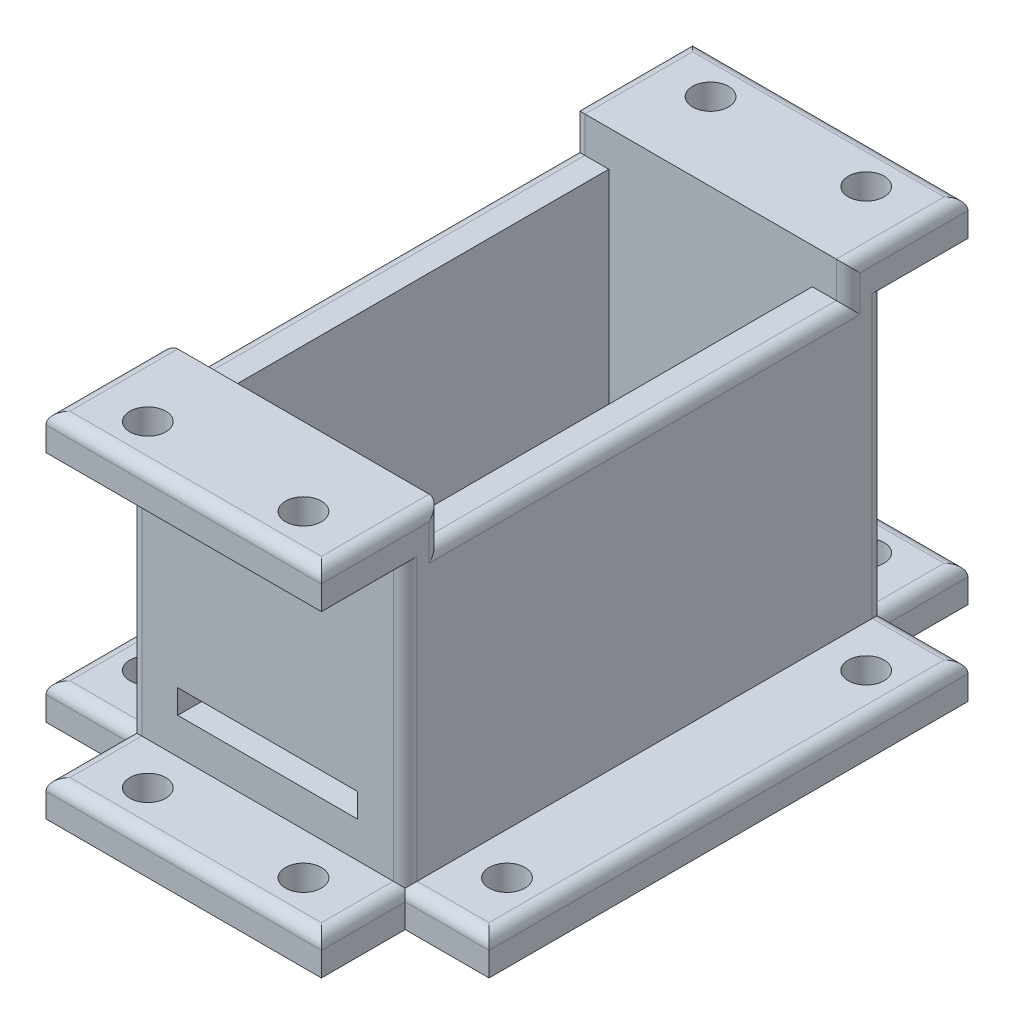
SolidWorks part; units mm, degrees
ref_plane "Alzado" through (0, 0, 0) normal (0, 0, 1) x (1, 0, 0)
ref_plane "Planta" through (0, 0, 0) normal (0, 1, 0) x (1, 0, 0)
ref_plane "Vista lateral" through (0, 0, 0) normal (1, 0, 0) x (0, 0, -1)
sketch "Croquis2" plane through (0, 0, 0) normal (0, 1, 0) x (1, 0, 0)
  line L1 (0, 0) -> (-23, 0)
  line L2 (0, 0) -> (0, 40)
  line L3 (0, 40) -> (-23, 40)
  line L4 (-23, 0) -> (-23, 40)
  dimension "D1" = 40
  dimension "D2" = 23
extrude "Saliente-Extruir1" add sketch "Croquis2" along normal blind 23.5
sketch "Croquis3" plane through (0, 23.5, 0) normal (0, 1, 0) x (1, 0, 0)
  line L0 (0, 40) -> (-23, 40) construction
  line L1 (-20, 37) -> (-3, 37)
  line L2 (-20, 37) -> (-20, 3)
  line L3 (-20, 3) -> (-3, 3)
  line L4 (-3, 37) -> (-3, 3)
  line L5 (-23, 40) -> (-23, 0) construction
  line L6 (-23, 0) -> (0, 0) construction
  line L7 (0, 0) -> (0, 40) construction
  dimension "D1" = 3
  dimension "D2" = 3
  dimension "D3" = 3
  dimension "D4" = 3
extrude "Cortar-Extruir1" cut sketch "Croquis3" against normal blind 13.5
sketch "Croquis4" plane through (0, 0, 0) normal (0, -1, 0) x (1, 0, 0)
  line L1 (0, -40) -> (-23, -40) construction
  line L2 (-17, -40) -> (-30, -40)
  line L3 (-17, -40) -> (-17, 0)
  line L4 (-17, 0) -> (-30, 0)
  line L5 (-30, -40) -> (-30, 0)
  line L6 (-23, -40) -> (-23, 0) construction
  line L7 (-23, -40) -> (-23, 0) construction
  line L8 (-23, -6) -> (0, -6)
  line L9 (-23, -6) -> (-23, 7)
  line L10 (-23, 7) -> (0, 7)
  line L11 (0, -6) -> (0, 7)
  line L12 (-23, 0) -> (0, 0) construction
  line L13 (0, 0) -> (0, -40) construction
  line L14 (-6, -40) -> (7, -40)
  line L15 (-6, -40) -> (-6, 0)
  line L16 (-6, 0) -> (7, 0)
  line L17 (7, -40) -> (7, 0)
  line L19 (-23, -34) -> (0, -34)
  line L20 (-23, -34) -> (-23, -47)
  line L21 (-23, -47) -> (0, -47)
  line L22 (0, -34) -> (0, -47)
  point P7 (-23, -20)
  line M13 (0, -40) -> (0, 0)
  line M14 (0, 0) -> (-23, 0)
  line M15 (-23, 0) -> (-23, -40)
  line M16 (-23, -40) -> (0, -40)
  dimension "D1" = 7
  dimension "D2" = 7
  dimension "D3" = 7
  dimension "D4" = 7
  dimension "D5" = 13
  dimension "D6" = 23
  dimension "D7" = 40
  dimension "D8" = 40
  dimension "D9" = 23
  dimension "D10" = 13
  dimension "D11" = 13
  dimension "D12" = 13
extrude "Saliente-Extruir6" add sketch "Croquis4" along normal blind 3 contours L19 L3 L8 M15 | L8 L3 M15 M14 | L5 L2 L4 M15 | L11 L10 L9 M14 | L19 L3 M15 M16 | L19 L3 L15 M16 | L19 L15 M16 M13 | L15 L19 L8 M13 | L15 L8 M13 M14 | L8 L15 L3 M14 | L14 L17 L16 M13
sketch "Croquis6" plane through (0, 0, 0) normal (0, 1, 0) x (1, 0, 0)
  line L0 (-30, 40) -> (-30, 0) construction
  line L1 (-30, 40) -> (-23, 40) construction
  line L2 (-23, 0) -> (-30, 0) construction
  line L3 (-23, 40) -> (-23, 47) construction
  line L4 (0, 40) -> (0, 47) construction
  line L5 (-23, 47) -> (0, 47) construction
  line L6 (-30, 20) -> (15.9373, 20) construction
  line L7 (-11.5, 47) -> (-11.5, -15.5258) construction
  circle A0 centre (-26.5, 5) radius 1.5
  circle A1 centre (-26.5, 35) radius 1.5
  circle A2 centre (-18, 43.5) radius 1.5
  circle A3 centre (-5, 43.5) radius 1.5
  circle A4 centre (3.5, 5) radius 1.5
  circle A5 centre (3.5, 35) radius 1.5
  circle A6 centre (-5, -3.5) radius 1.5
  circle A7 centre (-18, -3.5) radius 1.5
  dimension "D1" = 3
  dimension "D2" = 3
  dimension "D3" = 3.5
  dimension "D5" = 5
  dimension "D6" = 3.5
  dimension "D7" = 3
  dimension "D8" = 3
  dimension "D9" = 5
  dimension "D10" = 5
  dimension "D11" = 3.5
  dimension "D12" = 3.5
  dimension "D4" = 5
extrude "Cortar-Extruir2" cut sketch "Croquis6" against normal through all
sketch "Croquis7" plane through (0, 23.5, 0) normal (0, 1, 0) x (1, 0, 0)
  line L1 (-23, 40) -> (-23, 0) construction
  line L2 (-23, 37) -> (0, 37)
  line L3 (-23, 37) -> (-23, 47)
  line L4 (-23, 47) -> (0, 47)
  line L5 (0, 37) -> (0, 47)
  line L6 (-3, 37) -> (-20, 37) construction
  line L10 (-20, 3) -> (-3, 3) construction
  line L13 (-23, 3) -> (0, 3)
  line L14 (-23, 3) -> (-23, -7)
  line L15 (-23, -7) -> (0, -7)
  line L16 (0, 3) -> (0, -7)
  circle A0 centre (-18, -3.5) radius 1.5
  circle A1 centre (-5, -3.5) radius 1.5
  circle A2 centre (-18, 43.5) radius 1.5
  circle A3 centre (-5, 43.5) radius 1.5
  dimension "D5" = 3
  dimension "D6" = 3
  dimension "D7" = 3
  dimension "D4" = 3
  dimension "D1" = 23
  dimension "D2" = 10
  dimension "D3" = 10
extrude "Saliente-Extruir7" add sketch "Croquis7" along normal blind 3
fillet "Redondeo1" radius 1 4 edges at (0, 11.75, 0) (-23, 11.75, 0)
fillet "Redondeo2" radius 1 16 edges at (-22.7071, 0, -39.7071) (-0.2929, 0, -39.7071) (-0.2929, 0, -0.2929) (-22.7071, 0, -0.2929) (3.5, 0, 0) (-23, 0, 3.5) (-11.5, 0, 7) (-30, 0, -20) (3.5, 0, -40) (7, 0, -20) (0, 0, 3.5) (-26.5, 0, 0) (-26.5, 0, -40) (0, 0, -43.5) (-23, 0, -43.5) (-11.5, 0, -47)
fillet "Redondeo3" radius 1 12 edges at (0, 25, -3) (-23, 25, -3) (0, 26.5, 2) (-23, 26.5, 2) (-11.5, 26.5, 7) (0, 26.5, -42) (-11.5, 26.5, -47) (-23, 26.5, -42)
sketch "Croquis8" plane through (0, -3, 0) normal (0, -1, 0) x (-1, 0, 0)
  line L1 (20, 3) -> (3, 3)
  line L2 (20, 3) -> (20, 37)
  line L3 (20, 37) -> (3, 37)
  line L4 (3, 3) -> (3, 37)
extrude "Cortar-Extruir3" cut sketch "Croquis8" against normal through all
sketch "Croquis9" plane through (0, 0, -40) normal (0, 0, -1) x (-1, 0, 0)
  line L0 (1, 23.5) -> (1, 0) construction
  line L1 (4, 5) -> (19, 5)
  line L2 (4, 5) -> (4, 3)
  line L3 (4, 3) -> (19, 3)
  line L4 (19, 5) -> (19, 3)
  line L5 (22, 0) -> (22, 23.5) construction
  line L6 (1, 0) -> (22, 0) construction
  dimension "D1" = 3
  dimension "D2" = 3
  dimension "D3" = 2
  dimension "D4" = 3
extrude "Cortar-Extruir4" cut sketch "Croquis9" against normal through all
